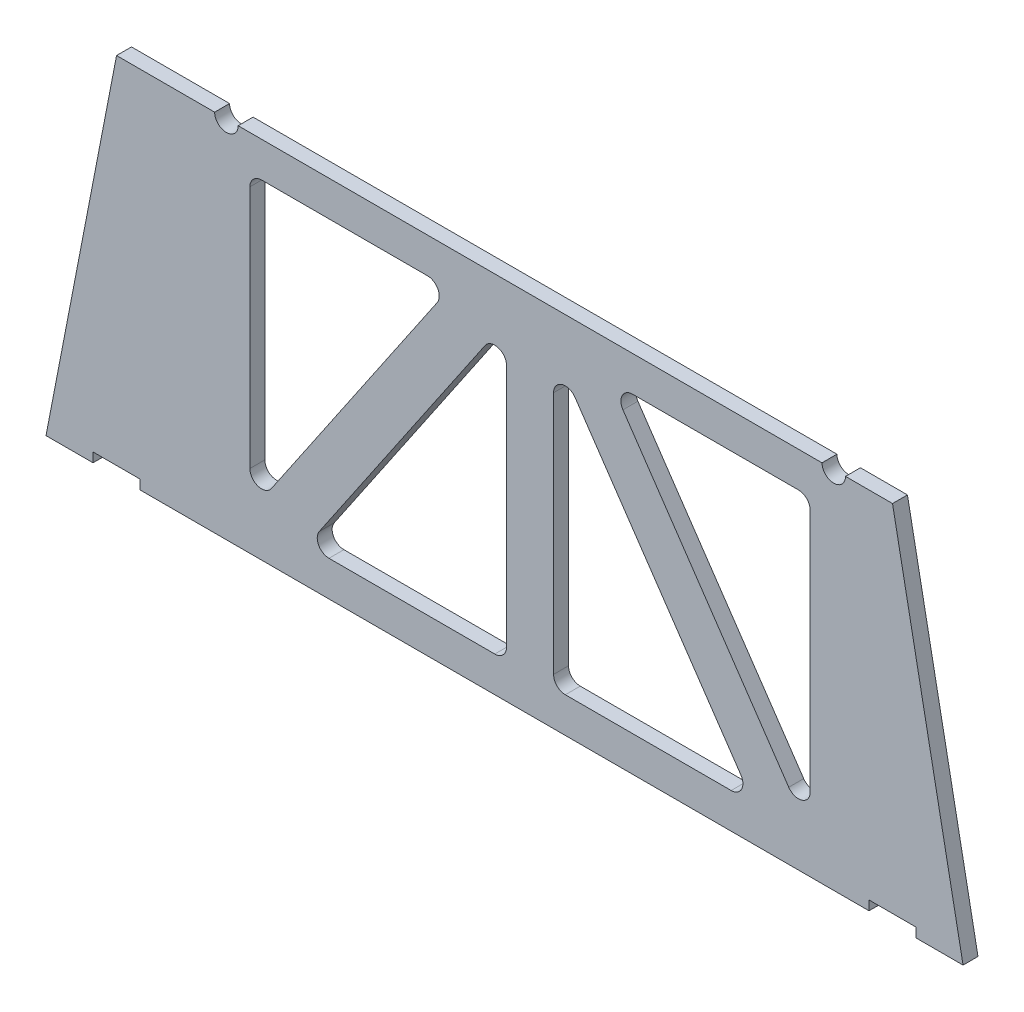
SolidWorks part; units mm, degrees
ref_plane "Front Plane" through (0, 0, 0) normal (0, 0, 1) x (1, 0, 0)
ref_plane "Top Plane" through (0, 0, 0) normal (0, 1, 0) x (1, 0, 0)
ref_plane "Right Plane" through (0, 0, 0) normal (1, 0, 0) x (0, 0, -1)
sketch "Sketch1" plane through (0, 0, 0) normal (0, 0, 1) x (1, 0, 0)
  line L0 (-165.8562, -77.5) -> (144.1438, -77.5)
  line L1 (184.1437, -77.5) -> (154.1437, 77.5)
  line L2 (154.1437, 77.5) -> (134.1438, 77.5)
  line L3 (-175.8562, 77.5) -> (-205.8562, -77.5)
  line L4 (-205.8562, -77.5) -> (-185.8562, -77.5)
  line L5 (-185.8562, -77.5) -> (-185.8562, -73.5)
  line L6 (-185.8562, -73.5) -> (-165.8562, -73.5)
  line L7 (-165.8562, -73.5) -> (-165.8562, -77.5)
  line L8 (-175.8562, 77.5) -> (-134.1438, 77.5)
  line L9 (144.1438, -77.5) -> (144.1438, -73.5)
  line L10 (144.1438, -73.5) -> (164.1438, -73.5)
  line L11 (164.1438, -73.5) -> (164.1438, -77.5)
  line L12 (164.1438, -77.5) -> (184.1437, -77.5)
  line L13 (-175.8562, 77.5) -> (-134.1438, 77.5)
  line L14 (0, -77.5) -> (0, 77.5) construction
  line L15 (-124.1437, 77.5) -> (124.1437, 77.5)
  line L16 (-119.1437, 57.5) -> (-119.1437, -46.249)
  line L17 (-110.0085, -49.0597) -> (-39.4913, 54.6893)
  line L18 (-114.1437, 62.5) -> (-43.6265, 62.5)
  line L19 (-89.6524, -54.6893) -> (-19.1352, 49.0597)
  line L20 (-10, 46.249) -> (-10, -57.5)
  line L21 (-85.5172, -62.5) -> (-15, -62.5)
  line L22 (15, -62.5) -> (85.5172, -62.5)
  line L23 (10, 46.249) -> (10, -57.5)
  line L24 (89.6524, -54.6893) -> (19.1352, 49.0597)
  line L25 (43.6265, 62.5) -> (114.1437, 62.5)
  line L26 (110.0085, -49.0597) -> (39.4913, 54.6893)
  line L27 (119.1437, 57.5) -> (119.1437, -46.249)
  arc A0 (-134.1438, 77.5) -> (-124.1437, 77.5) centre (-129.1438, 77.5) ccw
  arc A1 (134.1438, 77.5) -> (124.1437, 77.5) centre (129.1438, 77.5) cw
  arc A2 (-119.1437, 57.5) -> (-114.1437, 62.5) centre (-114.1437, 57.5) cw
  arc A3 (-110.0085, -49.0597) -> (-119.1437, -46.249) centre (-114.1437, -46.249) cw
  arc A4 (-39.4913, 54.6893) -> (-43.6265, 62.5) centre (-43.6265, 57.5) ccw
  arc A5 (-10, 46.249) -> (-19.1352, 49.0597) centre (-15, 46.249) ccw
  arc A6 (-15, -62.5) -> (-10, -57.5) centre (-15, -57.5) ccw
  arc A7 (-85.5172, -62.5) -> (-89.6524, -54.6893) centre (-85.5172, -57.5) cw
  arc A8 (10, 46.249) -> (19.1352, 49.0597) centre (15, 46.249) cw
  arc A9 (10, -57.5) -> (15, -62.5) centre (15, -57.5) ccw
  arc A10 (85.5172, -62.5) -> (89.6524, -54.6893) centre (85.5172, -57.5) ccw
  arc A11 (43.6265, 62.5) -> (39.4913, 54.6893) centre (43.6265, 57.5) ccw
  arc A12 (119.1437, 57.5) -> (114.1437, 62.5) centre (114.1437, 57.5) ccw
  arc A13 (110.0085, -49.0597) -> (119.1437, -46.249) centre (114.1437, -46.249) ccw
  point P15 (0, -77.5)
  point P29 (0, 0)
  point P37 (-119.1437, 62.5)
  point P40 (-119.1437, -62.5)
  point P43 (-34.1825, 62.5)
  point P46 (-10, 62.5)
  point P49 (-10, -62.5)
  point P52 (-94.9613, -62.5)
  point P55 (10, 62.5)
  point P58 (10, -62.5)
  point P61 (94.9613, -62.5)
  point P64 (34.1825, 62.5)
  point P67 (119.1437, 62.5)
  point P70 (119.1437, -62.5)
  dimension "D18" = 5
  dimension "D1" = 20
  dimension "D2" = 20
  dimension "D3" = 20
  dimension "D4" = 268.2875
  dimension "D5" = 15
  dimension "D6" = 10
  dimension "D7" = 20
  dimension "D8" = 4
  dimension "D9" = 10
  dimension "D10" = 310
  dimension "D11" = 5
  dimension "D13" = 20
  dimension "D14" = 10
  dimension "D15" = 15
  dimension "D16" = 155
  dimension "D17" = 5
extrude "Extrude1" add sketch "Sketch1" along normal blind 6.35 contours L0 L14 L15 A0 L8 L3 L4 L5 L6 L7 L16 L18 L17 L21 L19 L20 | L14 L0 L9 L10 L11 L12 L1 L2 A1 L15 L25 L27 L26 L24 L22 L23 region at (-163.2794, -75.5, 0) region at (2.4069, 0, 0)
